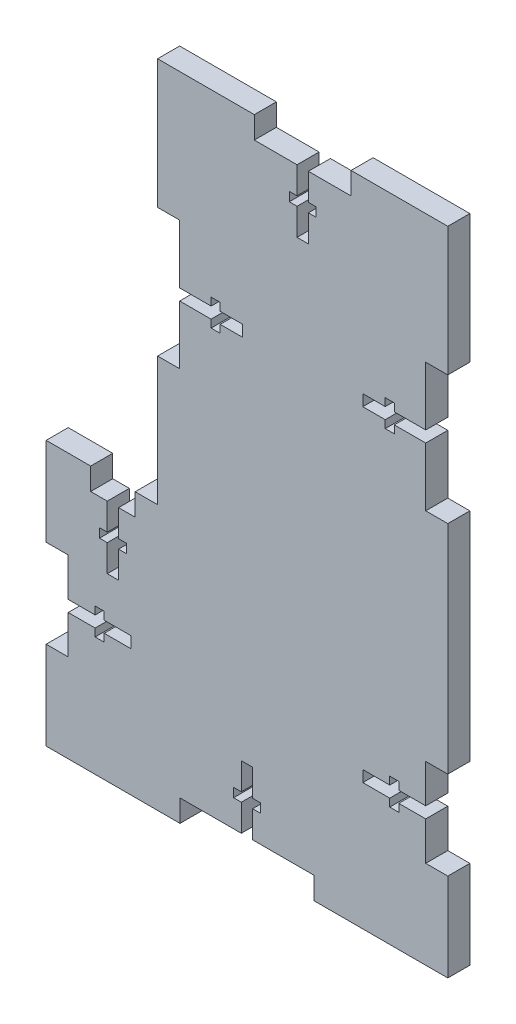
SolidWorks part; units mm, degrees
material "ABS PC"
ref_plane "Front Plane" through (0, 0, 0) normal (0, 0, 1) x (1, 0, 0)
ref_plane "Top Plane" through (0, 0, 0) normal (0, 1, 0) x (1, 0, 0)
ref_plane "Right Plane" through (0, 0, 0) normal (1, 0, 0) x (0, 0, -1)
sketch "Sketch1" plane through (0, 0, 0) normal (0, 0, 1) x (1, 0, 0)
  line L1 (-46.228, -30.48) -> (46.228, -30.48)
  line L2 (-46.228, -30.48) -> (-46.228, 30.48)
  line L3 (-46.228, 30.48) -> (46.228, 30.48)
  line L4 (46.228, -30.48) -> (46.228, 30.48)
  line L5 (-46.228, -30.48) -> (46.228, 30.48) construction
  line L6 (-46.228, 30.48) -> (46.228, -30.48) construction
  point P0 (0, 0)
  dimension "D1" = 92.456
  dimension "D2" = 60.96
extrude "Boss-Extrude1" add sketch "Sketch1" along normal blind 5.08
sketch "Sketch2" plane through (0, 0, 5.08) normal (0, 0, 1) x (1, 0, 0)
  line L1 (-35.9833, 30.48) -> (-25.7387, 30.48)
  line L2 (-35.9833, 30.48) -> (-35.9833, 25.4)
  line L3 (-35.9833, 25.4) -> (-25.7387, 25.4)
  line L4 (-25.7387, 30.48) -> (-25.7387, 25.4)
  line L5 (46.228, 30.48) -> (-46.228, 30.48) construction
  line L6 (0, 0) -> (46.228, 0) construction
  line L7 (46.228, -30.48) -> (46.228, 30.48) construction
  dimension "D1" = 10.2447
  dimension "D2" = 5.08
  dimension "D3" = 10.2447
extrude "Cut-Extrude1" cut sketch "Sketch2" against normal through all
sketch "Sketch3" plane through (0, 0, 5.08) normal (0, 0, 1) x (1, 0, 0)
  line L0 (-46.228, 30.48) -> (-46.228, -30.48) construction
  line L1 (-46.228, 10.16) -> (-41.148, 10.16)
  line L2 (-46.228, 10.16) -> (-46.228, -10.16)
  line L3 (-46.228, -10.16) -> (-41.148, -10.16)
  line L4 (-41.148, 10.16) -> (-41.148, -10.16)
  line L5 (0, 0) -> (0, 39.951) construction
  line L6 (46.228, -10.16) -> (41.148, -10.16)
  line L7 (46.228, 10.16) -> (46.228, -10.16)
  line L8 (46.228, 10.16) -> (41.148, 10.16)
  line L9 (41.148, 10.16) -> (41.148, -10.16)
  dimension "D1" = 5.08
  dimension "D2" = 20.32
  dimension "D3" = 20.32
extrude "Cut-Extrude2" cut sketch "Sketch3" against normal through all
sketch "Sketch4" plane through (0, 0, 5.08) normal (0, 0, 1) x (1, 0, 0)
  line L0 (0, 0) -> (-41.148, 0) construction
  line L1 (-41.148, -10.16) -> (-41.148, 10.16) construction
  line L2 (0, 0) -> (0, 28.5152) construction
  line L3 (-41.148, 1.3017) -> (-26.67, 1.3017)
  line L4 (-41.148, 1.3017) -> (-41.148, -1.3018)
  line L5 (-41.148, -1.3018) -> (-26.67, -1.3018)
  line L6 (-26.67, 1.3017) -> (-26.67, -1.3018)
  line L7 (26.67, 1.3018) -> (26.67, -1.3018)
  line L8 (41.148, -1.3017) -> (26.67, -1.3018)
  line L9 (41.148, 1.3017) -> (41.148, -1.3017)
  line L10 (41.148, 1.3017) -> (26.67, 1.3018)
  line L11 (-46.228, -10.16) -> (-46.228, 10.16) construction
  point P9 (-26.67, 0)
  dimension "D1" = 1.3017
  dimension "D2" = 19.558
extrude "Cut-Extrude3" cut sketch "Sketch4" against normal through all
sketch "Sketch5" plane through (0, 0, 5.08) normal (0, 0, 1) x (1, 0, 0)
  line L0 (-30.861, 25.4) -> (-30.861, 4.7969) construction
  line L1 (-35.9833, 25.4) -> (-25.7387, 25.4) construction
  line L2 (0, 0) -> (35.9654, 0) construction
  line L3 (-29.5593, 25.4) -> (-32.1628, 25.4)
  line L4 (-29.5593, 25.4) -> (-29.5593, 10.922)
  line L5 (-29.5593, 10.922) -> (-32.1628, 10.922)
  line L6 (-32.1628, 25.4) -> (-32.1628, 10.922)
  point P11 (-30.861, 25.4)
  dimension "D1" = 2.6035
  dimension "D3" = 14.478
extrude "Cut-Extrude4" cut sketch "Sketch5" against normal through all
sketch "Sketch6" plane through (0, 0, 5.08) normal (0, 0, 1) x (1, 0, 0)
  line L0 (-33.909, 1.3018) -> (-33.909, -1.3018) construction
  line L1 (-26.67, 1.3017) -> (-41.148, 1.3017) construction
  line L2 (-41.148, -1.3018) -> (-26.67, -1.3018) construction
  line L3 (-29.5593, 18.161) -> (-32.1628, 18.161) construction
  line L4 (-29.5593, 25.4) -> (-29.5593, 10.922) construction
  line L5 (-32.1628, 10.922) -> (-32.1628, 25.4) construction
  line L6 (-29.5593, 18.161) -> (-33.9471, 18.161) construction
  line L7 (-33.9471, 19.2024) -> (-27.7749, 19.2024)
  line L8 (-33.9471, 19.2024) -> (-33.9471, 17.1196)
  line L9 (-33.9471, 17.1196) -> (-27.7749, 17.1196)
  line L10 (-27.7749, 19.2024) -> (-27.7749, 17.1196)
  line L11 (0, 0) -> (19.2929, 0) construction
  line L12 (0, 0) -> (0, 14.5303) construction
  line L17 (-33.909, -1.3018) -> (-33.909, -3.0861) construction
  line L18 (-34.9504, 3.0861) -> (-32.8676, 3.0861)
  line L19 (-34.9504, 3.0861) -> (-34.9504, -3.0861)
  line L20 (-34.9504, -3.0861) -> (-32.8676, -3.0861)
  line L21 (-32.8676, 3.0861) -> (-32.8676, -3.0861)
  line L22 (-30.861, 10.922) -> (-30.861, 17.1196) construction
  line L23 (-29.5593, 10.922) -> (-32.1628, 10.922) construction
  line L24 (-26.67, 0) -> (-32.8676, 0) construction
  line L25 (-26.67, -1.3018) -> (-26.67, 1.3017) construction
  line L26 (34.9504, -3.0861) -> (32.8676, -3.0861)
  line L27 (32.8676, 3.0861) -> (32.8676, -3.0861)
  line L28 (34.9504, 3.0861) -> (34.9504, -3.0861)
  line L29 (34.9504, 3.0861) -> (32.8676, 3.0861)
  dimension "D1" = 6.1722
  dimension "D2" = 2.0828
  dimension "D3" = 2.0828
  dimension "D4" = 6.1722
extrude "Cut-Extrude5" cut sketch "Sketch6" against normal through all
sketch "Sketch7" plane through (0, 0, 5.08) normal (0, 0, 1) x (1, 0, 0)
  line L0 (46.228, 30.48) -> (46.228, 119.38)
  line L1 (46.228, 119.38) -> (-20.574, 119.38)
  line L2 (-20.574, 119.38) -> (-20.574, 30.48)
  line L3 (46.228, 30.48) -> (-25.7387, 30.48) construction
  line L60 (-29.5593, 19.2024) -> (-27.7749, 19.2024)
  line L61 (-27.7749, 19.2024) -> (-27.7749, 17.1196)
  line L62 (-27.7749, 17.1196) -> (-29.5593, 17.1196)
  line L63 (-29.5593, 10.922) -> (-32.1628, 10.922)
  line L64 (-32.1628, 17.1196) -> (-33.9471, 17.1196)
  line L65 (-33.9471, 17.1196) -> (-33.9471, 19.2024)
  line L66 (-33.9471, 19.2024) -> (-32.1628, 19.2024)
  line L67 (-32.1628, 25.4) -> (-35.9833, 25.4)
  line L68 (-29.5593, 25.4) -> (-29.5593, 19.2024)
  line L70 (-29.5593, 17.1196) -> (-29.5593, 10.922)
  line L72 (41.148, -1.3018) -> (34.9504, -1.3017)
  line L73 (34.9504, -1.3017) -> (34.9504, -3.0861)
  line L74 (34.9504, -3.0861) -> (32.8676, -3.0861)
  line L75 (32.8676, -3.0861) -> (32.8676, -1.3017)
  line L76 (32.8676, -1.3017) -> (26.67, -1.3018)
  line L77 (26.67, -1.3018) -> (26.67, 1.3018)
  line L78 (26.67, 1.3018) -> (32.8676, 1.3018)
  line L79 (32.8676, 1.3018) -> (32.8676, 3.0861)
  line L80 (32.8676, 3.0861) -> (34.9504, 3.0861)
  line L81 (34.9504, 3.0861) -> (34.9504, 1.3018)
  line L82 (34.9504, 1.3018) -> (41.148, 1.3017)
  line L83 (41.148, 1.3017) -> (41.148, 10.16)
  line L84 (41.148, 10.16) -> (46.228, 10.16)
  line L85 (46.228, 10.16) -> (46.228, 30.48)
  line L86 (46.228, 30.48) -> (-25.7387, 30.48)
  line L87 (-25.7387, 30.48) -> (-25.7387, 25.4)
  line L88 (-25.7387, 25.4) -> (-29.5593, 25.4)
  line L89 (-32.1628, 10.922) -> (-32.1628, 17.1196)
  line L91 (-32.1628, 19.2024) -> (-32.1628, 25.4)
  line L101 (-35.9833, 25.4) -> (-35.9833, 30.48)
  line L102 (-35.9833, 30.48) -> (-46.228, 30.48)
  line L103 (-46.228, 30.48) -> (-46.228, 10.16)
  line L104 (-46.228, 10.16) -> (-41.148, 10.16)
  line L105 (-41.148, 10.16) -> (-41.148, 1.3017)
  line L106 (-41.148, 1.3017) -> (-34.9504, 1.3017)
  line L107 (-34.9504, 1.3017) -> (-34.9504, 3.0861)
  line L108 (-34.9504, 3.0861) -> (-32.8676, 3.0861)
  line L109 (-32.8676, 3.0861) -> (-32.8676, 1.3017)
  line L110 (-32.8676, 1.3017) -> (-26.67, 1.3017)
  line L111 (-26.67, 1.3017) -> (-26.67, -1.3018)
  line L112 (-26.67, -1.3018) -> (-32.8676, -1.3018)
  line L113 (-32.8676, -1.3018) -> (-32.8676, -3.0861)
  line L114 (-32.8676, -3.0861) -> (-34.9504, -3.0861)
  line L115 (-34.9504, -3.0861) -> (-34.9504, -1.3018)
  line L116 (-34.9504, -1.3018) -> (-41.148, -1.3018)
  line L117 (-41.148, -1.3018) -> (-41.148, -10.16)
  line L118 (-41.148, -10.16) -> (-46.228, -10.16)
  line L119 (-46.228, -10.16) -> (-46.228, -30.48)
  line L120 (-46.228, -30.48) -> (46.228, -30.48)
  line L137 (46.228, -30.48) -> (46.228, -10.16)
  line L138 (46.228, -10.16) -> (41.148, -10.16)
  line L139 (41.148, -10.16) -> (41.148, -1.3018)
  line L154 (46.228, 30.48) -> (-20.574, 30.48)
  dimension "D1" = 88.9
  dimension "D2" = 66.802
  dimension "D3" = 0
extrude "Boss-Extrude2" add sketch "Sketch7" against normal blind 5.08
sketch "Sketch8" plane through (0, 0, 5.08) normal (0, 0, 1) x (1, 0, 0)
  line L0 (-46.228, -30.48) -> (46.228, -30.48) construction
  line L1 (15.4093, -30.48) -> (-15.4093, -30.48)
  line L2 (15.4093, -30.48) -> (15.4093, -25.4)
  line L3 (15.4093, -25.4) -> (-15.4093, -25.4)
  line L4 (-15.4093, -30.48) -> (-15.4093, -25.4)
  dimension "D1" = 5.08
  dimension "D2" = 30.8187
  dimension "D3" = 30.8187
extrude "Cut-Extrude6" cut sketch "Sketch8" against normal through all
sketch "Sketch10" plane through (0, 0, 5.08) normal (0, 0, 1) x (1, 0, 0)
  line L0 (15.4093, -25.4) -> (-15.4093, -25.4) construction
  line L1 (1.3017, -25.4) -> (-1.3017, -25.4)
  line L2 (1.3017, -25.4) -> (1.3017, -10.922)
  line L3 (1.3017, -10.922) -> (-1.3018, -10.922)
  line L4 (-1.3017, -25.4) -> (-1.3018, -10.922)
  line L5 (0, -10.922) -> (0, 0) construction
  dimension "D1" = 2.6035
  dimension "D2" = 14.478
extrude "Cut-Extrude7" cut sketch "Sketch10" against normal through all
sketch "Sketch11" plane through (0, 0, 5.08) normal (0, 0, 1) x (1, 0, 0)
  line L0 (3.0861, -18.161) -> (3.0861, -25.4) construction
  line L1 (15.4093, -25.4) -> (1.3017, -25.4) construction
  line L2 (-3.0861, -17.1196) -> (3.0861, -17.1196)
  line L3 (-3.0861, -17.1196) -> (-3.0861, -19.2024)
  line L4 (-3.0861, -19.2024) -> (3.0861, -19.2024)
  line L5 (3.0861, -17.1196) -> (3.0861, -19.2024)
  line L6 (-1.3018, -10.922) -> (-1.3017, -25.4) construction
  point P8 (-1.3018, -19.2024)
  dimension "D1" = 2.0828
  dimension "D2" = 6.1722
  dimension "D3" = 7.239
  dimension "D4" = 1.7844
extrude "Cut-Extrude8" cut sketch "Sketch11" against normal through all
sketch "Sketch12" plane through (0, 0, 5.08) normal (0, 0, 1) x (1, 0, 0)
  line L0 (46.228, 10.16) -> (46.228, 119.38) construction
  line L1 (46.228, 60.1133) -> (41.148, 60.1133)
  line L2 (46.228, 60.1133) -> (46.228, 89.7467)
  line L3 (46.228, 89.7467) -> (41.148, 89.7467)
  line L4 (41.148, 60.1133) -> (41.148, 89.7467)
  line L5 (12.827, 119.38) -> (12.827, 42.6911) construction
  line L6 (46.228, 119.38) -> (-20.574, 119.38) construction
  line L7 (-15.494, 60.1133) -> (-15.494, 89.7467)
  line L8 (-20.574, 89.7467) -> (-15.494, 89.7467)
  line L9 (-20.574, 60.1133) -> (-20.574, 89.7467)
  line L10 (-20.574, 60.1133) -> (-15.494, 60.1133)
  dimension "D1" = 5.08
  dimension "D2" = 29.6333
  dimension "D3" = 29.6333
extrude "Cut-Extrude9" cut sketch "Sketch12" against normal through all
sketch "Sketch13" plane through (0, 0, 5.08) normal (0, 0, 1) x (1, 0, 0)
  line L0 (26.67, 74.93) -> (41.148, 74.93) construction
  line L1 (41.148, 89.7467) -> (41.148, 60.1133) construction
  line L2 (12.827, 119.38) -> (12.827, 63.8669) construction
  line L3 (46.228, 119.38) -> (-20.574, 119.38) construction
  line L4 (-15.494, 73.6282) -> (-15.494, 76.2318)
  line L5 (26.67, 73.6282) -> (41.148, 73.6282)
  line L6 (26.67, 73.6282) -> (26.67, 76.2317)
  line L7 (26.67, 76.2317) -> (41.148, 76.2318)
  line L8 (41.148, 73.6282) -> (41.148, 76.2318)
  line L9 (-1.016, 76.2318) -> (-15.494, 76.2318)
  line L10 (-1.016, 73.6282) -> (-1.016, 76.2318)
  line L11 (-1.016, 73.6282) -> (-15.494, 73.6282)
  line L12 (12.827, 130.1398) -> (12.827, 119.38) construction
  line L13 (14.1288, 119.38) -> (11.5252, 119.38)
  line L14 (14.1288, 119.38) -> (14.1288, 99.822)
  line L15 (14.1288, 99.822) -> (11.5253, 99.822)
  line L16 (11.5252, 119.38) -> (11.5253, 99.822)
  dimension "D1" = 2.6035
  dimension "D2" = 14.478
  dimension "D3" = 2.6035
  dimension "D4" = 19.558
extrude "Cut-Extrude10" cut sketch "Sketch13" against normal through all
sketch "Sketch14" plane through (0, 0, 5.08) normal (0, 0, 1) x (1, 0, 0)
  line L0 (33.909, 93.7894) -> (41.148, 93.7894) construction
  line L1 (33.909, 71.8439) -> (31.8262, 71.8439)
  line L2 (33.909, 71.8439) -> (33.909, 78.0161)
  line L3 (33.909, 78.0161) -> (31.8262, 78.0161)
  line L4 (31.8262, 71.8439) -> (31.8262, 78.0161)
  line L5 (41.148, 89.7467) -> (41.148, 76.2318) construction
  line L6 (41.148, 76.2318) -> (26.67, 76.2318) construction
  line L7 (12.827, 119.38) -> (12.827, -38.735) construction
  line L9 (-8.255, 78.0161) -> (-6.1722, 78.0161)
  line L10 (-8.255, 71.8439) -> (-8.255, 78.0161)
  line L11 (-6.1722, 71.8439) -> (-6.1722, 78.0161)
  line L12 (-8.255, 71.8439) -> (-6.1722, 71.8439)
  line L14 (14.1288, 119.38) -> (11.5252, 119.38) construction
  line L15 (11.5252, 119.38) -> (11.5252, 99.822) construction
  line L16 (15.9131, 106.0196) -> (9.7409, 106.0196)
  line L17 (15.9131, 106.0196) -> (15.9131, 108.1024)
  line L18 (15.9131, 108.1024) -> (9.7409, 108.1024)
  line L19 (9.7409, 106.0196) -> (9.7409, 108.1024)
  line L20 (9.7409, 107.061) -> (9.7409, 119.38) construction
  line L21 (11.5252, 119.38) -> (-20.574, 119.38) construction
  point P8 (31.8262, 76.2318)
  point P25 (11.5252, 106.0196)
  dimension "D1" = 2.0828
  dimension "D2" = 6.1722
  dimension "D3" = 7.239
  dimension "D4" = 1.7844
  dimension "D5" = 2.0828
  dimension "D6" = 6.1722
  dimension "D7" = 1.7844
  dimension "D8" = 12.319
extrude "Cut-Extrude11" cut sketch "Sketch14" against normal through all
sketch "Sketch15" plane through (0, 0, 5.08) normal (0, 0, 1) x (1, 0, 0)
  line L0 (46.228, 119.38) -> (14.1288, 119.38) construction
  line L1 (23.9607, 119.38) -> (1.6933, 119.38)
  line L2 (23.9607, 119.38) -> (23.9607, 114.3)
  line L3 (23.9607, 114.3) -> (1.6933, 114.3)
  line L4 (1.6933, 119.38) -> (1.6933, 114.3)
  dimension "D1" = 5.08
  dimension "D2" = 22.2673
  dimension "D3" = 22.2673
extrude "Cut-Extrude12" cut sketch "Sketch15" against normal through all
equation "\"Length\"= \"Length@Box.SLDASM\""
equation "\"D1@Sketch1\"  = \"Length\" + 2 * \"Material\""
equation "\"Width\"= \"Short Height@Box.SLDASM\""
equation "\"D2@Sketch1\" = \"Width\" + 2 * \"Material\""
equation "\"Material\"= \"Material@Box.SLDASM\""
equation "\"D1@Boss-Extrude1\" = \"Material\""
equation "\"D1@Sketch2\"=(\"Length\" -\"Over Hang@Box.SLDASM\"+\"Material\"*2)/3"
equation "\"D2@Sketch2\"= \"Material\""
equation "\"D3@Sketch2\"=(\"Length\" -\"Over Hang@Box.SLDASM\"+\"Material\"*2)/3"
equation "\"D1@Sketch3\"=\"Material\""
equation "\"D2@Sketch3\"=(\"Width\" +\"Material\"*2)/3"
equation "\"D3@Sketch3\"=(\"Width\" +\"Material\"*2)/3"
equation "\"Diameter of Screw\"= \"Diameter of Screw@Box.SLDASM\""
equation "\"Length of screw\"= \"Length of Screw@Box.SLDASM\""
equation "\"D3@Sketch5\"= \"Length of screw\" - \"Material\""
equation "\"D1@Sketch5\" = \"Diameter of Screw\""
equation "\"D1@Sketch4\"= \"Diameter of Screw\" /2"
equation "\"D2@Sketch4\"=\"Length of screw\""
equation "\"Diameter of Nut\"= \"Diameter of Nut@Box.SLDASM\""
equation "\"D1@Sketch6\"=\"Diameter of Nut\""
equation "\"Height of Nut\"= \"Height of Nut@Box.SLDASM\""
equation "\"D3@Sketch6\"= \"Height of Nut\""
equation "\"D4@Sketch6\"=\"Diameter of Nut\""
equation "\"D2@Sketch6\"=\"Height of Nut\""
equation "\"D1@Sketch7\"= \"Long Height@Box.SLDASM\"-\"Short Height@Box.SLDASM\""
equation "\"D2@Sketch7\" = \"Over Hang@Box.SLDASM\" + \"Material\""
equation "\"D1@Boss-Extrude2\" = \"Material\""
equation "\"D1@Sketch8\"= \"Material\""
equation "\"D2@Sketch8\"=(\"Length\" + \"Material\"*2)/3"
equation "\"D3@Sketch8\"=(\"Length\" + \"Material\"*2)/3"
equation "\"D1@Sketch10\"=\"Diameter of Screw\""
equation "\"D2@Sketch10\"=\"Length of screw\" - \"Material\""
equation "\"D3@Sketch11\" = ( \"Length of screw\" - \"Material\" ) / 2"
equation "\"D4@Sketch11\"= ( \"Diameter of Nut\"-\"Diameter of Screw\" )/2"
equation "\"D1@Sketch12\"=\"Material\""
equation "\"D2@Sketch12\"=(\"Long Height@Box.SLDASM\"-\"Short Height@Box.SLDASM\")/3"
equation "\"D3@Sketch12\"=(\"Long Height@Box.SLDASM\"-\"Short Height@Box.SLDASM\")/3"
equation "\"D1@Sketch13\"=\"Diameter of Screw\""
equation "\"D2@Sketch13\"=\"Length of screw\"-\"Material\""
equation "\"D1@Sketch14\"=\"Height of Nut\""
equation "\"D2@Sketch14\"=\"Diameter of Nut\""
equation "\"D3@Sketch14\"=(\"Length of screw\"-\"Material\")/2"
equation "\"D4@Sketch14\"=(\"Diameter of Nut\"-\"Diameter of Screw\")/2"
equation "\"D1@Sketch15\"= \"Material\""
equation "\"D2@Sketch15\"=(\"Material\"+ \"over hang@Box.SLDASM\" )/3"
equation "\"D3@Sketch15\"=(\"Material\" + \"over hang@Box.SLDASM\" )/3"
equation "\"D3@Sketch13\"=\"Diameter of Screw\""
equation "\"D4@Sketch13\"=\"Length of screw\""
equation "\"D5@Sketch14\"=\"Height of Nut\""
equation "\"D6@Sketch14\"=\"Diameter of Nut\""
equation "\"D7@Sketch14\"=(\"Diameter of Nut\"-\"Diameter of Screw\")/2"
equation "\"D8@Sketch14\"=(\"Length of screw\"-\"Material\")/2 + \"Material\""
